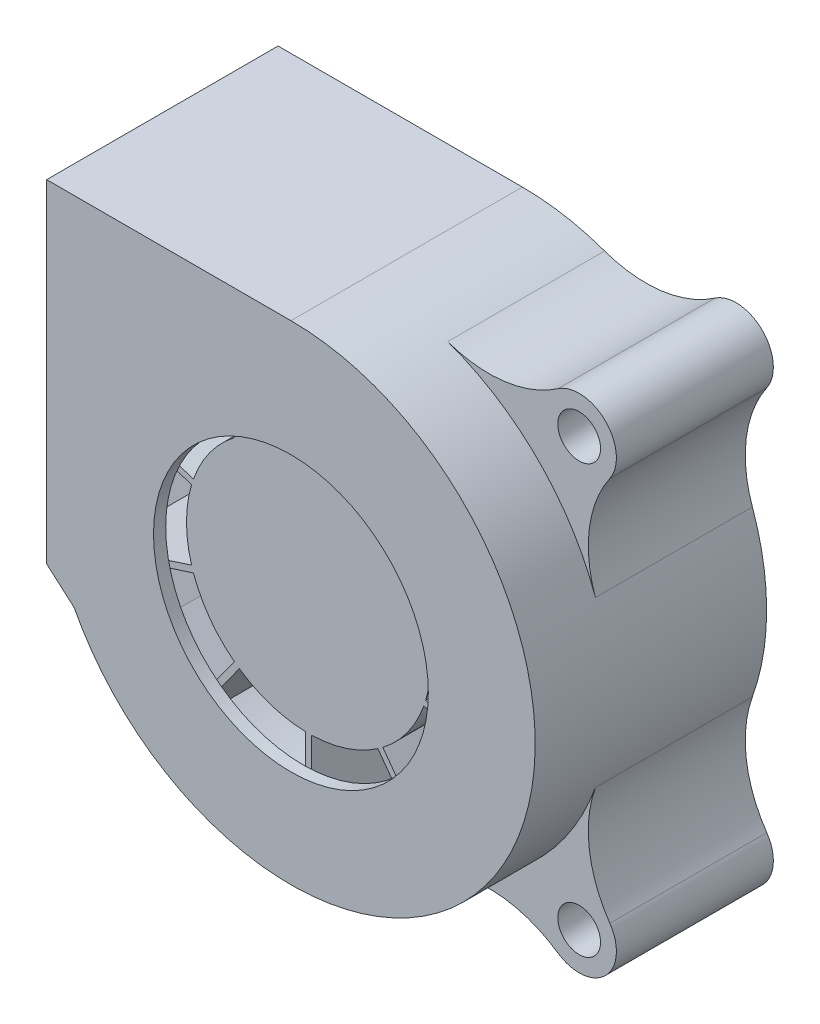
SolidWorks part; units mm, degrees
ref_plane "Alzado" through (0, 0, 0) normal (0, 0, 1) x (1, 0, 0)
ref_plane "Planta" through (0, 0, 0) normal (0, 1, 0) x (1, 0, 0)
ref_plane "Vista lateral" through (0, 0, 0) normal (1, 0, 0) x (0, 0, -1)
sketch "Croquis1" plane through (0, 0, 0) normal (0, 0, 1) x (1, 0, 0)
  line L0 (0, 20) -> (-20, 20)
  line L1 (-16.1618, -11.8484) -> (-20, -7.25)
  line L2 (-20, -7.25) -> (-20, 20)
  line L3 (-11.82, -16.1334) -> (-15.3433, -19.6567)
  line L4 (-17.5, -17.5) -> (17.5, -17.5) construction
  line L5 (-17.5, -17.5) -> (-17.5, 17.5) construction
  line L6 (-17.5, 17.5) -> (17.5, 17.5) construction
  line L7 (17.5, -17.5) -> (17.5, 17.5) construction
  line L8 (-17.5, -17.5) -> (17.5, 17.5) construction
  line L9 (-17.5, 17.5) -> (17.5, -17.5) construction
  line L10 (-16.1618, -11.8484) -> (-19.6567, -15.3433)
  line L11 (11.82, -16.1334) -> (15.3433, -19.6567)
  line L12 (16.1334, -11.82) -> (19.6567, -15.3433)
  line L13 (15.3433, 19.6567) -> (11.82, 16.1334)
  line L14 (19.6567, 15.3433) -> (16.1334, 11.82)
  arc A0 (-11.82, -16.1334) -> (11.82, -16.1334) centre (0, 0) ccw
  circle A1 centre (17.5, 17.5) radius 1.75
  circle A2 centre (17.5, -17.5) radius 1.75
  circle A3 centre (-17.5, -17.5) radius 1.75
  arc A4 (-19.6567, -15.3433) -> (-15.3433, -19.6567) centre (-17.5, -17.5) ccw
  arc A5 (15.3433, -19.6567) -> (19.6567, -15.3433) centre (17.5, -17.5) ccw
  arc A6 (19.6567, 15.3433) -> (15.3433, 19.6567) centre (17.5, 17.5) ccw
  arc A7 (11.82, 16.1334) -> (0, 20) centre (0, 0) ccw
  arc A8 (16.1334, -11.82) -> (16.1334, 11.82) centre (0, 0) ccw
  dimension "D1" = 40
  dimension "D5" = 3.5
  dimension "D6" = 3.5
  dimension "D7" = 3.5
  dimension "D8" = 1.3
  dimension "D9" = 1.3
  dimension "D10" = 1.3
  dimension "D2" = 27.25
  dimension "D3" = 20
  dimension "D4" = 35
extrude "Saliente-Extruir1" add sketch "Croquis1" along normal blind 18.95
sketch "Croquis2" plane through (0, 0, 18.95) normal (0, 0, 1) x (1, 0, 0)
  line L0 (0, 0) -> (0, -20) construction
  circle A0 centre (0, -0.75) radius 11.25
  arc A1 (-11.82, -16.1334) -> (11.82, -16.1334) centre (0, 0) ccw construction
  dimension "D1" = 22.5
  dimension "D2" = 8
extrude "Cortar-Extruir1" cut sketch "Croquis2" against normal blind 15.95
ref_plane "Plano1" through (0, 0, 17.95) normal (0, 0, 1) x (1, 0, 0)
sketch "Croquis3" plane through (0, 0, 17.95) normal (0, 0, 1) x (1, 0, 0)
  line L0 (-20, 19) -> (-20, -5.6894)
  line L1 (-20, 20) -> (-20, -7.25) construction
  line L22 (0, 19) -> (-20, 19)
  line L23 (0, 19) -> (-20, 19)
  line L24 (-15.3941, -11.2076) -> (-11.229, -15.3267)
  line L25 (-19.2323, -6.6092) -> (-15.3941, -11.2076)
  line L26 (-20, -5.6894) -> (-15.3941, -11.2076)
  line L27 (11.229, -15.3267) -> (15.3267, -11.229)
  line L28 (11.229, 15.3267) -> (15.3267, 11.229)
  arc A20 (11.229, 15.3267) -> (0, 19) centre (0, 0) ccw
  arc A21 (11.229, 15.3267) -> (0, 19) centre (0, 0) ccw
  arc A27 (15.3267, -11.229) -> (15.3267, 11.229) centre (0, 0) ccw
  arc A28 (15.3267, -11.229) -> (15.3267, 11.229) centre (0, 0) ccw
  arc A30 (-11.229, -15.3267) -> (11.229, -15.3267) centre (0, 0) ccw
  arc A31 (-11.229, -15.3267) -> (11.229, -15.3267) centre (0, 0) ccw
  dimension "D1" = 1
  dimension "D3" = 1
  dimension "D4" = 1
  dimension "D5" = 1
  dimension "D6" = 1
extrude "Cortar-Extruir2" cut sketch "Croquis3" against normal offset from surface (16.95 mm away) 1 up to face at (19.25, -17.5, 0)
fillet "Redondeo1" radius 10 6 edges at (11.82, 16.1334, 9.475) (-16.1618, -11.8484, 9.475) (-11.82, -16.1334, 9.475) (11.82, -16.1334, 9.475) (16.1334, -11.82, 9.475) (16.1334, 11.82, 9.475)
sketch "Croquis4" plane through (0, 0, 18.95) normal (0, 0, 1) x (1, 0, 0)
  line L0 (-20, -7.25) -> (-6.7331, -18.8326)
  line L2 (18.8326, -6.7331) -> (17.6539, -9.3416)
  line L10 (0, 20) -> (-20, 20)
  line L11 (-20, 20) -> (-20, -7.25)
  line L19 (0, 20) -> (-20, 20) construction
  line L20 (-20, 20) -> (-20, -7.25) construction
  circle A0 centre (17.5, 17.5) radius 1.75 construction
  circle A1 centre (17.5, -17.5) radius 1.75 construction
  circle A2 centre (-17.5, -17.5) radius 1.75 construction
  circle A3 centre (17.5, 17.5) radius 1.75
  circle A4 centre (17.5, -17.5) radius 1.75
  circle A5 centre (-17.5, -17.5) radius 1.75
  circle A6 centre (0, 0) radius 20
  arc A7 (6.7331, 18.8326) -> (18.8326, 6.7331) centre (0, 0) cw
  arc A12 (6.7331, 18.8326) -> (15.7704, 20.0122) centre (10.0997, 28.2488) ccw
  arc A13 (6.7331, 18.8326) -> (0, 20) centre (0, 0) ccw
  arc A14 (-20.204, -16.0889) -> (-20, -7.25) centre (-29.0694, -11.4625) ccw
  arc A15 (-20.204, -16.0889) -> (-15.7704, -20.0122) centre (-17.5, -17.5) ccw
  arc A16 (-6.7331, -18.8326) -> (-15.7704, -20.0122) centre (-10.0997, -28.2488) ccw
  arc A17 (-6.7331, -18.8326) -> (6.7331, -18.8326) centre (0, 0) ccw
  arc A18 (15.7704, -20.0122) -> (6.7331, -18.8326) centre (10.0997, -28.2488) ccw
  arc A19 (15.7704, -20.0122) -> (20.0122, -15.7704) centre (17.5, -17.5) ccw
  arc A20 (18.8326, -6.7331) -> (20.0122, -15.7704) centre (28.2488, -10.0997) ccw
  arc A21 (18.8326, -6.7331) -> (18.8326, 6.7331) centre (0, 0) ccw
  arc A22 (20.0122, 15.7704) -> (18.8326, 6.7331) centre (28.2488, 10.0997) ccw
  arc A23 (20.0122, 15.7704) -> (15.7704, 20.0122) centre (17.5, 17.5) ccw
  arc A24 (6.7331, 18.8326) -> (15.7704, 20.0122) centre (10.0997, 28.2488) ccw
  arc A25 (6.7331, 18.8326) -> (0, 20) centre (0, 0) ccw construction
  arc A26 (-20.204, -16.0889) -> (-20, -7.25) centre (-29.0694, -11.4625) ccw
  arc A27 (-20.204, -16.0889) -> (-15.7704, -20.0122) centre (-17.5, -17.5) ccw
  arc A28 (-6.7331, -18.8326) -> (-15.7704, -20.0122) centre (-10.0997, -28.2488) ccw
  arc A29 (-6.7331, -18.8326) -> (6.7331, -18.8326) centre (0, 0) ccw construction
  arc A30 (15.7704, -20.0122) -> (6.7331, -18.8326) centre (10.0997, -28.2488) ccw
  arc A31 (15.7704, -20.0122) -> (20.0122, -15.7704) centre (17.5, -17.5) ccw
  arc A32 (18.8326, -6.7331) -> (20.0122, -15.7704) centre (28.2488, -10.0997) ccw
  arc A33 (18.8326, -6.7331) -> (18.8326, 6.7331) centre (0, 0) ccw construction
  arc A34 (20.0122, 15.7704) -> (18.8326, 6.7331) centre (28.2488, 10.0997) ccw
  arc A35 (20.0122, 15.7704) -> (15.7704, 20.0122) centre (17.5, 17.5) ccw
  dimension "D1" = 0
extrude "Cortar-Extruir3" cut sketch "Croquis4" against normal offset from surface (6.1 mm away) 12.85
sketch "Croquis7" plane through (0, 0, 0) normal (0, 0, -1) x (-1, 0, 0)
  line L0 (0, 0) -> (0, -11.3) construction
  line L1 (-2.25, -11.3) -> (2.25, -11.3)
  line L2 (-2.25, -11.3) -> (-2.25, -14.8)
  line L3 (-2.25, -14.8) -> (2.25, -14.8)
  line L4 (2.25, -11.3) -> (2.25, -14.8)
  circle A0 centre (0, 0) radius 10.675 construction
  dimension "D1" = 21.35
  dimension "D2" = 3.5
  dimension "D3" = 11.3
  dimension "D4" = 4.5
extrude "Cortar-Extruir4" cut sketch "Croquis7" against normal up to next
sketch "Croquis8" plane through (0, 0, 1) normal (0, 0, 1) x (1, 0, 0)
  line L0 (-0.25, 17.9983) -> (-0.25, 9.9969)
  line L1 (0.25, 9.9969) -> (0.25, 17.9983)
  line L2 (0, 0) -> (0, 22.3553) construction
  line L3 (-0.25, 9.9969) -> (0, 0)
  line L4 (0, 0) -> (5.6738, 8.2346)
  arc A0 (0.25, 17.9983) -> (-0.25, 17.9983) centre (0, 0) ccw
  arc A1 (5.6738, 8.2346) -> (0.25, 9.9969) centre (0, 0) ccw
  dimension "D2" = 20
  dimension "D4" = 18
  dimension "D1" = 0.5
  dimension "D3" = 36
extrude "Saliente-Extruir2" add sketch "Croquis8" along normal blind 16 from offset 0.5 separate body
pattern_circular "MatrizC1" count 10 over 360 about axis through (0, 0, 0) along (0, 0, 1) of bodies 106
combine bodies "Combinar1" operation type add bodies to combine 115 106 107 108 109 110 111 112 113 114
